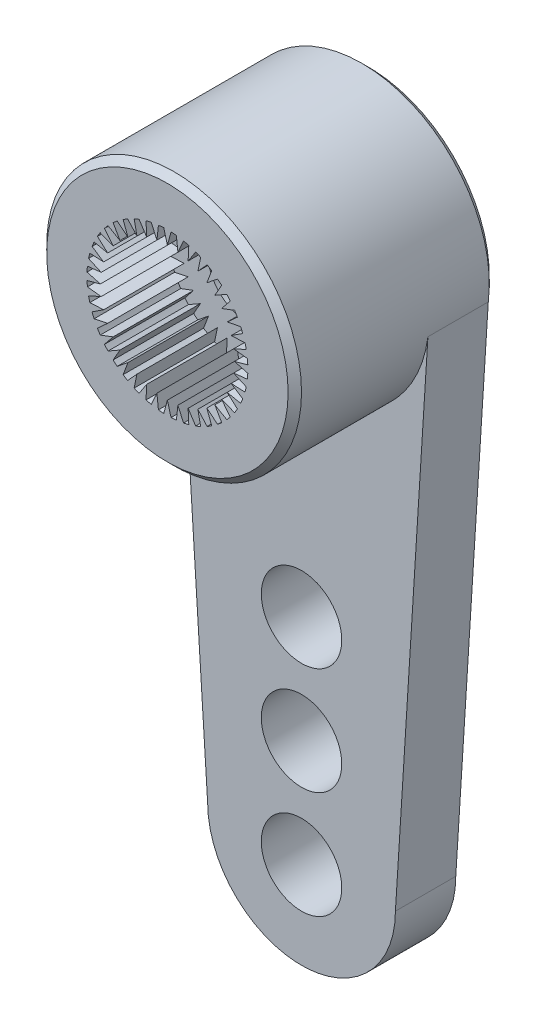
SolidWorks part; units mm, degrees
ref_plane "Front Plane" through (0, 0, 0) normal (0, 0, 1) x (1, 0, 0)
ref_plane "Top Plane" through (0, 0, 0) normal (0, 1, 0) x (1, 0, 0)
ref_plane "Right Plane" through (0, 0, 0) normal (1, 0, 0) x (0, 0, -1)
sketch "Sketch1" plane through (0, 0, 0) normal (0, 0, 1) x (1, 0, 0)
  line L0 (-2.9388, 0.6027) -> (-2.4692, 0.3911)
  line L1 (-2.4692, 0.3911) -> (-2.9812, 0.335)
  line L2 (-2.9969, 0.1355) -> (-2.5, 0)
  line L3 (-2.5, 0) -> (-2.9969, -0.1355)
  line L4 (-2.9812, -0.335) -> (-2.4692, -0.3911)
  line L5 (-2.4692, -0.3911) -> (-2.9388, -0.6027)
  line L6 (-2.8921, -0.7972) -> (-2.3776, -0.7725)
  line L7 (-2.3776, -0.7725) -> (-2.8084, -1.055)
  line L8 (-2.7318, -1.2398) -> (-2.2275, -1.135)
  line L9 (-2.2275, -1.135) -> (-2.6088, -1.4813)
  line L10 (-2.5042, -1.6519) -> (-2.0225, -1.4695)
  line L11 (-2.0225, -1.4695) -> (-2.3449, -1.8712)
  line L12 (-2.215, -2.0233) -> (-1.7678, -1.7678)
  line L13 (-1.7678, -1.7678) -> (-2.0233, -2.215)
  line L14 (-1.8712, -2.3449) -> (-1.4695, -2.0225)
  line L15 (-1.4695, -2.0225) -> (-1.6519, -2.5042)
  line L16 (-1.4813, -2.6088) -> (-1.135, -2.2275)
  line L17 (-1.135, -2.2275) -> (-1.2398, -2.7318)
  line L18 (-1.055, -2.8084) -> (-0.7725, -2.3776)
  line L19 (-0.7725, -2.3776) -> (-0.7972, -2.8921)
  line L20 (-0.6027, -2.9388) -> (-0.3911, -2.4692)
  line L21 (-0.3911, -2.4692) -> (-0.335, -2.9812)
  line L22 (-0.1355, -2.9969) -> (0, -2.5)
  line L23 (0, -2.5) -> (0.1355, -2.9969)
  line L24 (0.335, -2.9812) -> (0.3911, -2.4692)
  line L25 (0.3911, -2.4692) -> (0.6027, -2.9388)
  line L26 (0.7972, -2.8921) -> (0.7725, -2.3776)
  line L27 (0.7725, -2.3776) -> (1.055, -2.8084)
  line L28 (1.2398, -2.7318) -> (1.135, -2.2275)
  line L29 (1.135, -2.2275) -> (1.4813, -2.6088)
  line L30 (1.6519, -2.5042) -> (1.4695, -2.0225)
  line L31 (1.4695, -2.0225) -> (1.8712, -2.3449)
  line L32 (2.0233, -2.215) -> (1.7678, -1.7678)
  line L33 (1.7678, -1.7678) -> (2.215, -2.0233)
  line L34 (2.3449, -1.8712) -> (2.0225, -1.4695)
  line L35 (2.0225, -1.4695) -> (2.5042, -1.6519)
  line L36 (2.6088, -1.4813) -> (2.2275, -1.135)
  line L37 (2.2275, -1.135) -> (2.7318, -1.2398)
  line L38 (2.8084, -1.055) -> (2.3776, -0.7725)
  line L39 (2.3776, -0.7725) -> (2.8921, -0.7972)
  line L40 (2.9388, -0.6027) -> (2.4692, -0.3911)
  line L41 (2.4692, -0.3911) -> (2.9812, -0.335)
  line L42 (2.9969, -0.1355) -> (2.5, 0)
  line L43 (2.5, 0) -> (2.9969, 0.1355)
  line L44 (2.9812, 0.335) -> (2.4692, 0.3911)
  line L45 (2.4692, 0.3911) -> (2.9388, 0.6027)
  line L46 (2.8921, 0.7972) -> (2.3776, 0.7725)
  line L47 (2.3776, 0.7725) -> (2.8084, 1.055)
  line L48 (2.7318, 1.2398) -> (2.2275, 1.135)
  line L49 (2.2275, 1.135) -> (2.6088, 1.4813)
  line L50 (2.5042, 1.6519) -> (2.0225, 1.4695)
  line L51 (2.0225, 1.4695) -> (2.3449, 1.8712)
  line L52 (2.215, 2.0233) -> (1.7678, 1.7678)
  line L53 (1.7678, 1.7678) -> (2.0233, 2.215)
  line L54 (1.8712, 2.3449) -> (1.4695, 2.0225)
  line L55 (1.4695, 2.0225) -> (1.6519, 2.5042)
  line L56 (1.4813, 2.6088) -> (1.135, 2.2275)
  line L57 (1.135, 2.2275) -> (1.2398, 2.7318)
  line L58 (1.055, 2.8084) -> (0.7725, 2.3776)
  line L59 (0.7725, 2.3776) -> (0.7972, 2.8921)
  line L60 (0.6027, 2.9388) -> (0.3911, 2.4692)
  line L61 (0.3911, 2.4692) -> (0.335, 2.9812)
  line L62 (0.1355, 2.9969) -> (0, 2.5)
  line L63 (0, 2.5) -> (-0.1355, 2.9969)
  line L64 (-0.335, 2.9812) -> (-0.3911, 2.4692)
  line L65 (-0.3911, 2.4692) -> (-0.6027, 2.9388)
  line L66 (-0.7972, 2.8921) -> (-0.7725, 2.3776)
  line L67 (-0.7725, 2.3776) -> (-1.055, 2.8084)
  line L68 (-1.2398, 2.7318) -> (-1.135, 2.2275)
  line L69 (-1.135, 2.2275) -> (-1.4813, 2.6088)
  line L70 (-1.6519, 2.5042) -> (-1.4695, 2.0225)
  line L71 (-1.4695, 2.0225) -> (-1.8712, 2.3449)
  line L72 (-2.0233, 2.215) -> (-1.7678, 1.7678)
  line L73 (-1.7678, 1.7678) -> (-2.215, 2.0233)
  line L74 (-2.3449, 1.8712) -> (-2.0225, 1.4695)
  line L75 (-2.0225, 1.4695) -> (-2.5042, 1.6519)
  line L76 (-2.6088, 1.4813) -> (-2.2275, 1.135)
  line L77 (-2.2275, 1.135) -> (-2.7318, 1.2398)
  line L78 (-2.8084, 1.055) -> (-2.3776, 0.7725)
  line L79 (-2.3776, 0.7725) -> (-2.8921, 0.7972)
  arc A0 (-2.9812, 0.335) -> (-2.9969, 0.1355) centre (0, 0) ccw
  arc A1 (-2.9969, -0.1355) -> (-2.9812, -0.335) centre (0, 0) ccw
  arc A2 (-2.9388, -0.6027) -> (-2.8921, -0.7972) centre (0, 0) ccw
  arc A3 (-2.8084, -1.055) -> (-2.7318, -1.2398) centre (0, 0) ccw
  arc A4 (-2.6088, -1.4813) -> (-2.5042, -1.6519) centre (0, 0) ccw
  arc A5 (-2.3449, -1.8712) -> (-2.215, -2.0233) centre (0, 0) ccw
  arc A6 (-2.0233, -2.215) -> (-1.8712, -2.3449) centre (0, 0) ccw
  arc A7 (-1.6519, -2.5042) -> (-1.4813, -2.6088) centre (0, 0) ccw
  arc A8 (-1.2398, -2.7318) -> (-1.055, -2.8084) centre (0, 0) ccw
  arc A9 (-0.7972, -2.8921) -> (-0.6027, -2.9388) centre (0, 0) ccw
  arc A10 (-0.335, -2.9812) -> (-0.1355, -2.9969) centre (0, 0) ccw
  arc A11 (0.1355, -2.9969) -> (0.335, -2.9812) centre (0, 0) ccw
  arc A12 (0.6027, -2.9388) -> (0.7972, -2.8921) centre (0, 0) ccw
  arc A13 (1.055, -2.8084) -> (1.2398, -2.7318) centre (0, 0) ccw
  arc A14 (1.4813, -2.6088) -> (1.6519, -2.5042) centre (0, 0) ccw
  arc A15 (1.8712, -2.3449) -> (2.0233, -2.215) centre (0, 0) ccw
  arc A16 (2.215, -2.0233) -> (2.3449, -1.8712) centre (0, 0) ccw
  arc A17 (2.5042, -1.6519) -> (2.6088, -1.4813) centre (0, 0) ccw
  arc A18 (2.7318, -1.2398) -> (2.8084, -1.055) centre (0, 0) ccw
  arc A19 (2.8921, -0.7972) -> (2.9388, -0.6027) centre (0, 0) ccw
  arc A20 (2.9812, -0.335) -> (2.9969, -0.1355) centre (0, 0) ccw
  arc A21 (2.9969, 0.1355) -> (2.9812, 0.335) centre (0, 0) ccw
  arc A22 (2.9388, 0.6027) -> (2.8921, 0.7972) centre (0, 0) ccw
  arc A23 (2.8084, 1.055) -> (2.7318, 1.2398) centre (0, 0) ccw
  arc A24 (2.6088, 1.4813) -> (2.5042, 1.6519) centre (0, 0) ccw
  arc A25 (2.3449, 1.8712) -> (2.215, 2.0233) centre (0, 0) ccw
  arc A26 (2.0233, 2.215) -> (1.8712, 2.3449) centre (0, 0) ccw
  arc A27 (1.6519, 2.5042) -> (1.4813, 2.6088) centre (0, 0) ccw
  arc A28 (1.2398, 2.7318) -> (1.055, 2.8084) centre (0, 0) ccw
  arc A29 (0.7972, 2.8921) -> (0.6027, 2.9388) centre (0, 0) ccw
  arc A30 (0.335, 2.9812) -> (0.1355, 2.9969) centre (0, 0) ccw
  arc A31 (-0.1355, 2.9969) -> (-0.335, 2.9812) centre (0, 0) ccw
  arc A32 (-0.6027, 2.9388) -> (-0.7972, 2.8921) centre (0, 0) ccw
  arc A33 (-1.055, 2.8084) -> (-1.2398, 2.7318) centre (0, 0) ccw
  arc A34 (-1.4813, 2.6088) -> (-1.6519, 2.5042) centre (0, 0) ccw
  arc A35 (-1.8712, 2.3449) -> (-2.0233, 2.215) centre (0, 0) ccw
  arc A36 (-2.215, 2.0233) -> (-2.3449, 1.8712) centre (0, 0) ccw
  arc A37 (-2.5042, 1.6519) -> (-2.6088, 1.4813) centre (0, 0) ccw
  arc A38 (-2.7318, 1.2398) -> (-2.8084, 1.055) centre (0, 0) ccw
  arc A39 (-2.8921, 0.7972) -> (-2.9388, 0.6027) centre (0, 0) ccw
  circle A40 centre (0, 0) radius 3
sketch "Sketch2" plane through (0, 0, 0) normal (0, 0, 1) x (1, 0, 0)
  line L0 (-12.25, 0) -> (12.25, 0) construction
  line L1 (0, 12.25) -> (0, -12.25) construction
  circle A0 centre (0, 0) radius 12.25
  circle A2 centre (0, 8.25) radius 1.5944
  circle A3 centre (0, -8.25) radius 1.5944
  circle A4 centre (-8.25, 0) radius 1.5944
  circle A5 centre (8.25, 0) radius 1.5944
  dimension "D1" = 16.5
  dimension "D2" = 24.5
  dimension "D3" = 16.5
  dimension "D4" = 8.25
  dimension "D5" = 8.25
extrude "Boss-Extrude1" add sketch "Sketch2" along normal blind 2
sketch "Sketch3" plane through (0, 0, 2) normal (0, 0, 1) x (1, 0, 0)
  circle A0 centre (0, 0) radius 1.5
extrude "Cut-Extrude1" cut sketch "Sketch3" against normal blind 2
sketch "Sketch4" plane through (0, 0, 2) normal (0, 0, 1) x (1, 0, 0)
  circle A0 centre (0, 0) radius 3
  circle A1 centre (0, 0) radius 4
extrude "Boss-Extrude2" add sketch "Sketch4" along normal blind 3
extrude "Boss-Extrude3" add sketch "Sketch1" along normal blind 3 from surface contours L2 A40 L3 | L0 A40 L1 | L78 A40 L79 | L76 A40 L77 | L74 A40 L75 | L72 A40 L73 | L70 A40 L71 | L68 A40 L69 | L66 A40 L67 | L64 A40 L65 | L62 A40 L63 | L60 A40 L61 | L58 A40 L59 | L56 A40 L57 | L54 A40 L55 | L52 A40 L53 | L50 A40 L51 | L48 A40 L49 | L46 A40 L47 | L44 A40 L45 | L42 A40 L43 | L40 A40 L41 | L38 A40 L39 | L36 A40 L37 | L34 A40 L35 | L32 A40 L33 | L30 A40 L31 | L28 A40 L29 | L26 A40 L27 | L24 A40 L25 | L22 A40 L23 | L20 A40 L21 | L18 A40 L19 | L16 A40 L17 | L14 A40 L15 | L12 A40 L13 | L10 A40 L11 | L8 A40 L9 | L6 A40 L7 | L4 A40 L5 region at (-2.7978, 0.4431, 0) region at (-2.694, 0.8753, 0) region at (-2.8327, 0, 0) region at (-2.5239, 1.286, 0) region at (-2.7978, -0.4431, 0) region at (-2.2917, 1.665, 0) region at (-2.694, -0.8753, 0) region at (-2.003, 2.003, 0) region at (-2.5239, -1.286, 0) region at (-1.665, 2.2917, 0) region at (-2.2917, -1.665, 0) region at (-1.286, 2.5239, 0) region at (-2.003, -2.003, 0) region at (-0.8753, 2.694, 0) region at (-1.665, -2.2917, 0) region at (-0.4431, 2.7978, 0) region at (-1.286, -2.5239, 0) region at (0, 2.8327, 0) region at (-0.8753, -2.694, 0) region at (0.4431, 2.7978, 0) region at (-0.4431, -2.7978, 0) region at (0.8753, 2.694, 0) region at (0, -2.8327, 0) region at (1.286, 2.5239, 0) region at (0.4431, -2.7978, 0) region at (1.665, 2.2917, 0) region at (0.8753, -2.694, 0) region at (2.003, 2.003, 0) region at (1.286, -2.5239, 0) region at (2.2917, 1.665, 0) region at (1.665, -2.2917, 0) region at (2.5239, 1.286, 0) region at (2.003, -2.003, 0) region at (2.694, 0.8753, 0) region at (2.2917, -1.665, 0) region at (2.7978, 0.4431, 0) region at (2.5239, -1.286, 0) region at (2.8327, 0, 0) region at (2.694, -0.8753, 0) region at (2.7978, -0.4431, 0) starting at face at (1.5, 0, 2)
sketch "Sketch5" plane through (0, 0, 0) normal (0, 0, -1) x (-1, 0, 0)
  circle A0 centre (0, 0) radius 3
  point P4 (0, 0)
extrude "Cut-Extrude2" cut sketch "Sketch5" against normal blind 0.5
sketch "Sketch6" plane through (0, 0, 2) normal (0, 0, 1) x (1, 0, 0)
  circle A0 centre (0, 0) radius 4.25
  circle A1 centre (0, 0) radius 12.25
extrude "Cut-Extrude3" cut sketch "Sketch6" against normal blind 10
sketch "Sketch7" plane through (0, 0, 2) normal (0, 0, 1) x (1, 0, 0)
  circle A1 centre (0, 0) radius 4.25
  circle A2 centre (0, 0) radius 4.25
  circle M2 centre (0, 0) radius 4
  circle M3 centre (0, 0) radius 4.25
  dimension "D1" = 0
extrude "Boss-Extrude5" add sketch "Sketch7" along normal up to surface (3 mm away) contours M3 M2 region at (-4.1298, 0, 2) up to face at (4, 0, 5)
sketch "Sketch8" plane through (0, 0, 0) normal (0, 0, -1) x (-1, 0, 0)
  circle A0 centre (0, 0) radius 4.25 construction
  circle A1 centre (0, 0) radius 4.25
  circle A2 centre (0, 0) radius 4.75
extrude "Boss-Extrude6" add sketch "Sketch8" against normal up to surface (5 mm away) up to face at (0, 0, 5)
sketch "Sketch9" plane through (0, 0, 0) normal (0, 0, -1) x (-1, 0, 0)
  circle A0 centre (0, 0) radius 3
  circle A1 centre (0, 0) radius 4.75
extrude "Boss-Extrude7" add sketch "Sketch9" along normal blind 2.5
chamfer "Chamfer2" distance 0.25 angle 45 1 edges at (4.75, 0, 5)
sketch "Sketch11" plane through (0, 0, -2.5) normal (0, 0, -1) x (-1, 0, 0)
  line L0 (0, 0) -> (0, -19.75) construction
  line L1 (-4.75, 0) -> (-3.5, -19.75)
  line L2 (4.75, 0) -> (3.5, -19.75)
  line L3 (0, 4.75) -> (0, -23.25) construction
  arc A1 (-3.5, -19.75) -> (3.5, -19.75) centre (0, -19.75) ccw
  circle A2 centre (0, 0) radius 4.75 construction
  arc A3 (-4.75, 0) -> (4.75, 0) centre (0, 0) ccw
  circle A5 centre (0, -16) radius 1.5
  circle A6 centre (0, -12) radius 1.5
  circle A7 centre (0, -20) radius 1.5
  point P1 (0, -23.25)
  point P3 (0, 4.75)
  circle M4 centre (0, 0) radius 4.75
  dimension "D1" = 3.5
  dimension "D2" = 28
  dimension "D3" = 20
  dimension "D4" = 16
  dimension "D5" = 12
extrude "Boss-Extrude8" add sketch "Sketch11" against normal blind 2.5 contours L1 A1 L2 A7 A6 A5 M4 region at (0, -4.9953, -2.5)
chamfer "Chamfer3" distance 0.5 angle 45 1 edges at (-3, 0, -2.5)
chamfer "Chamfer4" distance 0.25 angle 45 7 edges at (4.106, -10.1744, -2.5) (-1.5, -20, -2.5) (-1.5, -16, -2.5) (-1.5, -12, -2.5) (0, 4.75, -2.5) (-4.106, -10.1744, -2.5) (0, -23.25, -2.5)
ref_axis "ServoAxis" through (0, 0, 0.5) along (0, 0, 1)
